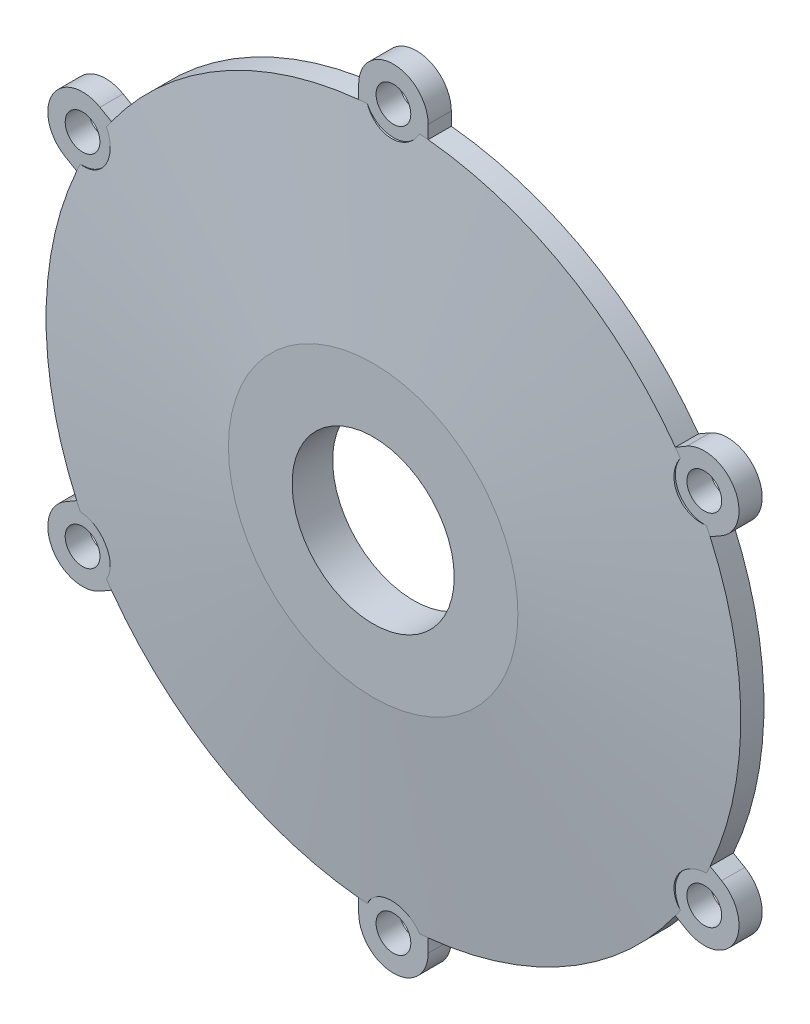
SolidWorks part; units mm, degrees
material "1060 Alloy"
ref_plane "Front Plane" through (0, 0, 0) normal (0, 0, 1) x (1, 0, 0)
ref_plane "Top Plane" through (0, 0, 0) normal (0, 1, 0) x (1, 0, 0)
ref_plane "Right Plane" through (0, 0, 0) normal (1, 0, 0) x (0, 0, -1)
sketch "Sketch1" plane through (0, 0, 0) normal (0, 0, 1) x (1, 0, 0)
  line L0 (-6, 62) -> (-6, 59.6992)
  line L1 (6, 62) -> (6, 59.6992)
  line L2 (50.6936, 36.1962) -> (48.7011, 35.0458)
  line L3 (56.6936, 25.8038) -> (54.7011, 24.6535)
  line L4 (56.6936, -25.8038) -> (54.7011, -24.6535)
  line L5 (50.6936, -36.1962) -> (48.7011, -35.0458)
  line L6 (6, -62) -> (6, -59.6992)
  line L7 (-6, -62) -> (-6, -59.6992)
  line L8 (-50.6936, -36.1962) -> (-48.7011, -35.0458)
  line L9 (-56.6936, -25.8038) -> (-54.7011, -24.6535)
  line L10 (-56.6936, 25.8038) -> (-54.7011, 24.6535)
  line L11 (-50.6936, 36.1962) -> (-48.7011, 35.0458)
  line L12 (0, 0) -> (6, 59.6992) construction
  circle A0 centre (0, 0) radius 57
  circle A1 centre (0, 0) radius 60
  arc A2 (6, 62) -> (-6, 62) centre (0, 62) ccw
  arc A3 (56.6936, 25.8038) -> (50.6936, 36.1962) centre (53.6936, 31) ccw
  arc A4 (50.6936, -36.1962) -> (56.6936, -25.8038) centre (53.6936, -31) ccw
  arc A5 (-6, -62) -> (6, -62) centre (0, -62) ccw
  arc A6 (-56.6936, -25.8038) -> (-50.6936, -36.1962) centre (-53.6936, -31) ccw
  arc A7 (-50.6936, 36.1962) -> (-56.6936, 25.8038) centre (-53.6936, 31) ccw
  dimension "D1" = 120
  dimension "D2" = 3
  dimension "D3" = 6
  dimension "D4" = 62
  dimension "D5" = 6
extrude "Boss-Extrude1" add sketch "Sketch1" along normal blind 4 contours L11 A7 L10 A1 | L1 A2 L0 A1 | L3 A3 L2 A1 | L5 A4 L4 A1 | L7 A5 L6 A1 | L9 A6 L8 A1 | A0 A1 region at (0, 63.4372, 0) region at (0, 58.3029, 0) region at (-54.9382, 31.7186, 0) region at (54.9382, 31.7186, 0) region at (-54.9382, -31.7186, 0) region at (54.9382, -31.7186, 0) region at (0, -63.4372, 0)
sketch "Sketch3" plane through (0, 0, 0) normal (0, 1, 0) x (1, 0, 0)
  line L0 (0, -4) -> (60, -4)
  line L1 (-6, -4) -> (6, -4) construction
  line L2 (60, -4) -> (25, -7.5)
  line L3 (25, -7.5) -> (0, -7.5)
  line L4 (0, -7.5) -> (0, -4)
  line L5 (48.7011, 0) -> (6, 0) construction
  dimension "D1" = 7.5
  dimension "D2" = 25
revolve "Revolve1" add sketch "Sketch3" angle 360 about L4
sketch "Sketch10" plane through (0, 0, 4) normal (0, 0, -1) x (-1, 0, 0)
  circle A1 centre (0, 0) radius 57
  circle A3 centre (0, 0) radius 57 construction
extrude "Boss-Extrude3" add sketch "Sketch10" along normal blind 1 contours A1 region at (0, 0, 4)
sketch "Sketch6" plane through (0, 0, 3) normal (0, 0, -1) x (-1, 0, 0)
  circle A0 centre (0, 0) radius 20
  dimension "D1" = 40
extrude "Boss-Extrude2" add sketch "Sketch6" along normal blind 2.5
sketch "Sketch4" plane through (0, 0, 7.5) normal (0, 0, 1) x (1, 0, 0)
  circle A0 centre (0, 0) radius 14
  dimension "D1" = 28
extrude "Cut-Extrude1" cut sketch "Sketch4" against normal through all
sketch "Sketch7" plane through (0, 0, 4) normal (0, 0, 1) x (1, 0, 0)
  circle A0 centre (0, 62) radius 3
  arc A1 (6, 62) -> (-6, 62) centre (0, 62) ccw construction
  dimension "D1" = 6
extrude "Cut-Extrude2" cut sketch "Sketch7" against normal through all
sketch "Sketch8" plane through (0, 0, 4) normal (0, 0, 1) x (1, 0, 0)
  circle A0 centre (0, 62) radius 5
  dimension "D1" = 10
extrude "Cut-Extrude3" cut sketch "Sketch8" along normal through all
pattern_circular "CirPattern1" count 6 over 360 about axis through (0, 0, 4) along (0, 0, 1) of "Cut-Extrude3", "Cut-Extrude2"
